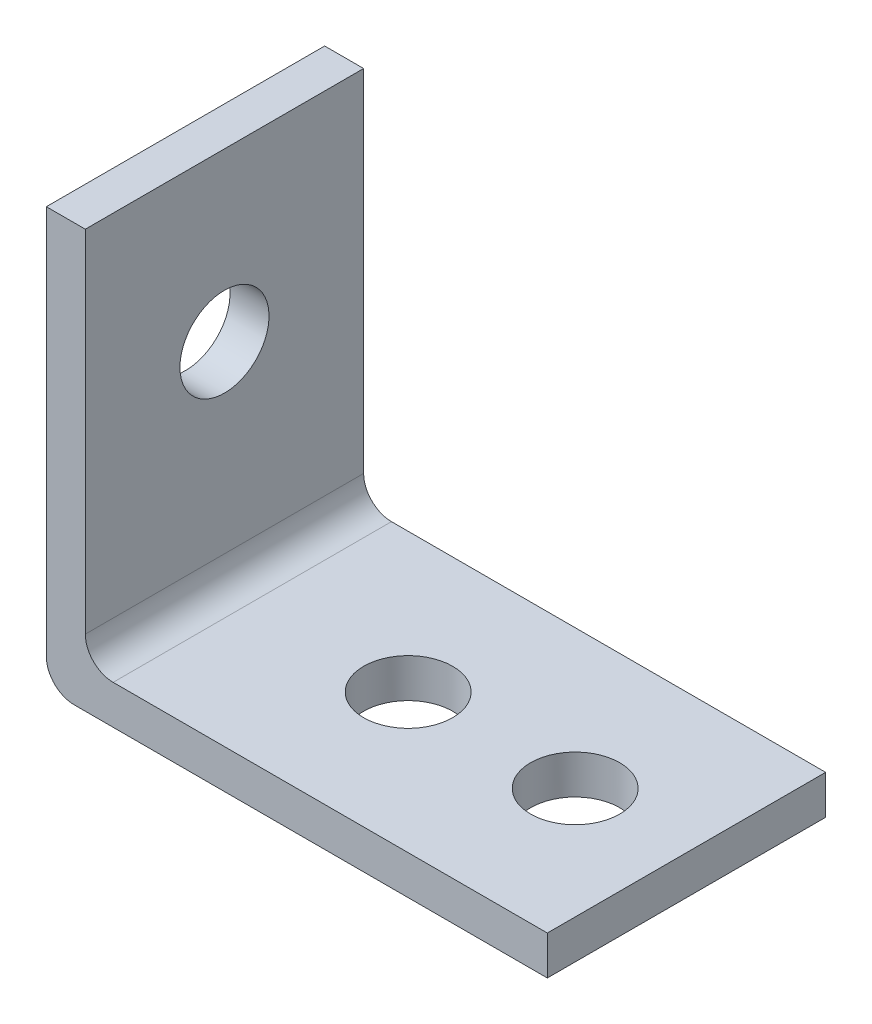
SolidWorks part; units mm, degrees
material "Plain Carbon Steel"
ref_plane "Front Plane" through (0, 0, 0) normal (0, 0, 1) x (1, 0, 0)
ref_plane "Top Plane" through (0, 0, 0) normal (0, 1, 0) x (1, 0, 0)
ref_plane "Right Plane" through (0, 0, 0) normal (1, 0, 0) x (0, 0, -1)
sketch "Sketch1" plane through (0, 0, 0) normal (0, 0, 1) x (1, 0, 0)
  line L0 (0, 0) -> (0, 19.05)
  line L1 (0, 19.05) -> (1.778, 19.05)
  line L2 (1.778, 19.05) -> (1.778, 1.778)
  line L3 (1.778, 1.778) -> (22.86, 1.778)
  line L4 (22.86, 1.778) -> (22.86, 0)
  line L5 (22.86, 0) -> (0, 0)
  dimension "D1" = 1.778
  dimension "D2" = 1.778
  dimension "D3" = 22.86
  dimension "D4" = 19.05
extrude "Boss-Extrude1" add sketch "Sketch1" against normal mid plane 12.7
sketch "Sketch2" plane through (0, 0, 0) normal (-1, 0, 0) x (0, 0, 1)
  line L0 (-6.35, 19.05) -> (6.35, 19.05) construction
  circle A0 centre (0, 11.43) radius 2.032
  dimension "D1" = 4.064
  dimension "D3" = 7.62
  dimension "D2" = 11.43
extrude "Cut-Extrude1" cut sketch "Sketch2" against normal up to next
sketch "Sketch3" plane through (0, 0, 0) normal (0, -1, 0) x (1, 0, 0)
  circle A0 centre (10.16, 0) radius 2.032
  dimension "D1" = 4.064
  dimension "D2" = 10.16
extrude "Cut-Extrude2" cut sketch "Sketch3" against normal up to next
fillet "Fillet2" radius 1.27 1 edges at (1.778, 1.778, 0)
fillet "Fillet3" radius 1.27 1 edges at (0, 0, 0)
pattern_linear "LPattern1" count 2 spacing 7.62 along (1, 0, 0) of "Cut-Extrude2"
